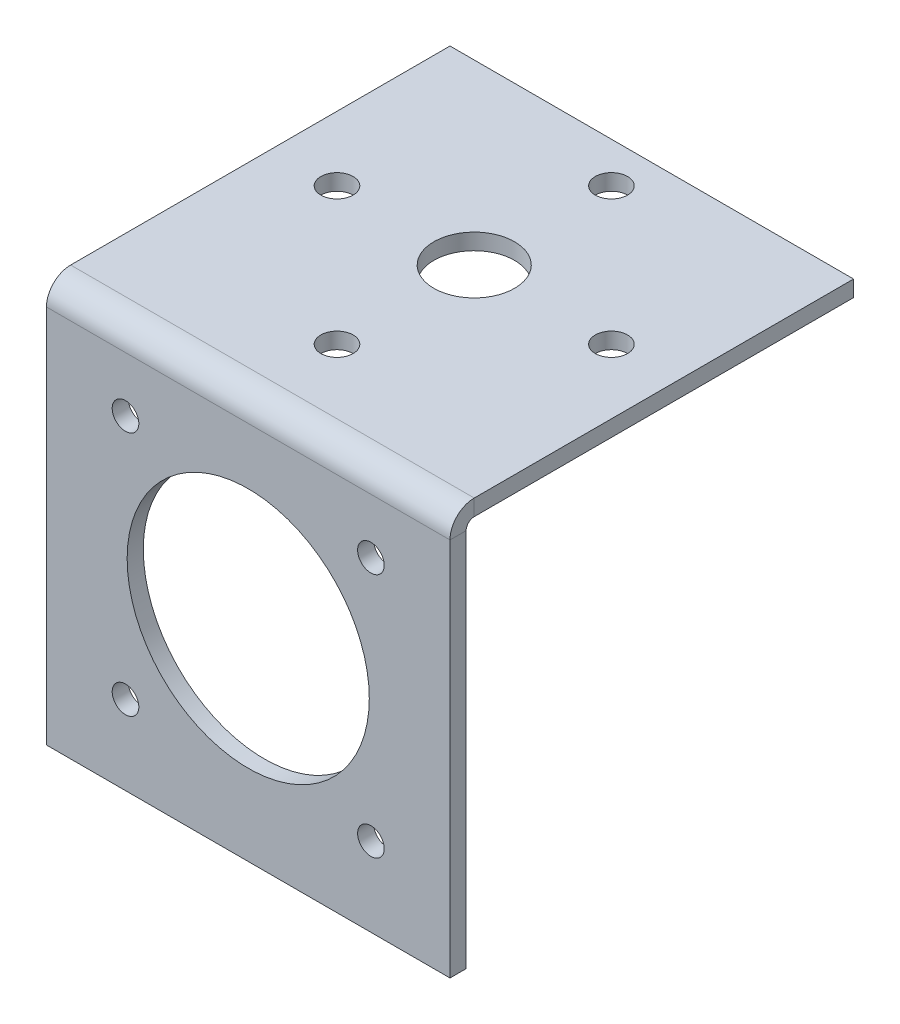
SolidWorks part; units mm, degrees
note: The reader was unsure of these and kept them because the rebuilt part matched: flange length of "边线-法兰1".
ref_plane "前视基准面" through (0, 0, 0) normal (0, 0, 1) x (1, 0, 0)
ref_plane "上视基准面" through (0, 0, 0) normal (0, 1, 0) x (1, 0, 0)
ref_plane "右视基准面" through (0, 0, 0) normal (1, 0, 0) x (0, 0, -1)
other "Configuration Table"
sketch "草图1" plane through (0, 0, 0) normal (0, 0, 1) x (1, 0, 0)
  line L1 (-25, -25) -> (25, -25)
  line L2 (-25, -25) -> (-25, 25)
  line L3 (-25, 25) -> (25, 25)
  line L4 (25, -25) -> (25, 25)
  line L5 (-25, -25) -> (25, 25) construction
  line L6 (-25, 25) -> (25, -25) construction
  point P0 (0, 0)
  dimension "D1" = 50
  dimension "D2" = 50
base flange "基体-法兰1" sketch "草图1" thickness 2 reverse thickness direction no parameters "D1"=0.7366
edge flange "边线-法兰1" sketch "草图8" flange angle 90 flange length 50 flange position material inside bend radius 1 thickness 2 relief rectangular parameters "D6"=10
sketch "草图8" plane through (0, 25, -2) normal (0, -1, 0) x (-1, 0, 0)
  line L2 (-25, 0) -> (-25, 48)
  line L3 (-25, 48) -> (25, 48)
  line L4 (25, 48) -> (25, 0)
  line L5 (25, 0) -> (-25, 0) construction
  line L6 (25, 0) -> (-25, 0)
bend "边线折弯1" bend radius 1 bend angle 90 parameters "D5"=1
sketch "草图9" plane through (0, 0, 0) normal (0, 0, 1) x (1, 0, 0)
  line L0 (0, 0) -> (-15.2028, 15.2028) construction
  line L1 (-25, -25) -> (25, -25) construction
  circle A0 centre (0, 0) radius 15
  circle A1 centre (0, 0) radius 21.5 construction
  circle A2 centre (-15.2028, 15.2028) radius 1.65
  circle A3 centre (15.2028, 15.2028) radius 1.65
  circle A4 centre (15.2028, -15.2028) radius 1.65
  circle A5 centre (-15.2028, -15.2028) radius 1.65
  point P17 (0, 0)
  dimension "D1" = 30
  dimension "D2" = 43
  dimension "D4" = 3.3
  dimension "D3" = 45
  dimension "D5" = 4
extrude "切除-拉伸2" cut sketch "草图9" against normal blind 10 normal cut yes
sketch "草图12" plane through (0, 25, 0) normal (0, 1, 0) x (1, 0, 0)
  line L0 (25, 0) -> (-25, 0) construction
  circle A0 centre (0, 28) radius 5
  circle A1 centre (0, 28) radius 17 construction
  circle A2 centre (0, 45) radius 2
  circle A3 centre (17, 28) radius 2
  circle A4 centre (0, 11) radius 2
  circle A5 centre (-17, 28) radius 2
  point P15 (0, 28)
  dimension "D1" = 10
  dimension "D3" = 34
  dimension "D4" = 4
  dimension "D2" = 28
  dimension "D5" = 4
extrude "切除-拉伸4" cut sketch "草图12" against normal blind 10 normal cut yes
sketch "折弯-线1" plane through (0, 0, 0) normal (0, 1, 0) x (1, 0, 0)
sketch "边界框1" plane through (0, 0, 0) normal (0, 1, 0) x (1, 0, 0)
sheet metal parameters "钣金6" thickness 2 parameters "D1"=0.7366
flat pattern "平展型式6" [suppressed]
sketch "折弯-线2" plane through (0, 0, 0) normal (0, 1, 0) x (1, 0, 0)
sketch "边界框2" [suppressed] plane through (0, 0, 0) normal (0, 1, 0) x (1, 0, 0)
sheet metal parameters "钣金7" thickness 2 parameters "D1"=0.7366
flat pattern "平展型式6" [suppressed]
sketch "折弯-线2" plane through (0, 0, 0) normal (0, 1, 0) x (1, 0, 0)
sketch "边界框2" [suppressed] plane through (0, 0, 0) normal (0, 1, 0) x (1, 0, 0)
bend of the flat pattern "展平-<边线折弯1>1"
sheet metal parameters "钣金8" thickness 2 parameters "D1"=0.7366
flat pattern "平展型式6" [suppressed]
sketch "折弯-线2" plane through (0, 0, 0) normal (0, 1, 0) x (1, 0, 0)
sketch "边界框2" [suppressed] plane through (0, 0, 0) normal (0, 1, 0) x (1, 0, 0)
bend of the flat pattern "展平-<边线折弯1>1"
sheet metal parameters "钣金9" thickness 2 parameters "D1"=0.7366
flat pattern "平展型式6" [suppressed]
sketch "折弯-线2" plane through (0, 0, 0) normal (0, 1, 0) x (1, 0, 0)
sketch "边界框2" [suppressed] plane through (0, 0, 0) normal (0, 1, 0) x (1, 0, 0)
bend of the flat pattern "展平-<边线折弯1>1"
